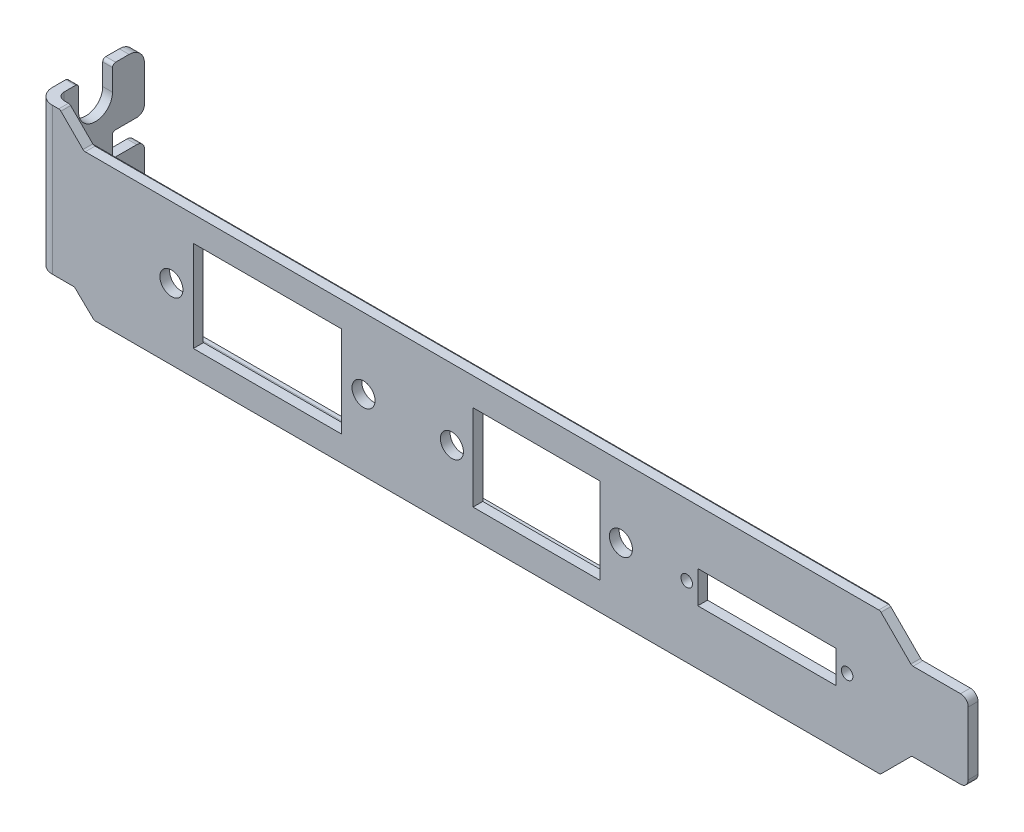
SolidWorks part; units mm, degrees
ref_plane "Front Plane" through (0, 0, 0) normal (0, 0, 1) x (1, 0, 0)
ref_plane "Top Plane" through (0, 0, 0) normal (0, 1, 0) x (1, 0, 0)
ref_plane "Right Plane" through (0, 0, 0) normal (1, 0, 0) x (0, 0, -1)
sketch "Sketch1" plane through (0, 0, 0) normal (0, 0, 1) x (1, 0, 0)
  line L0 (0, 2.48) -> (4.88, 2.48)
  line L5 (7.45, 0) -> (109.76, 0)
  line L6 (0, 2.48) -> (0, 21.53)
  line L7 (6.11, 18.42) -> (109.73, 18.42)
  line L8 (113.85, 4.09) -> (113.85, 14.3) construction
  line L9 (4.88, 2.48) -> (7.45, 0)
  line L10 (109.76, 0) -> (113.85, 4.09)
  line L11 (109.73, 18.42) -> (113.85, 14.3)
  line L12 (6.11, 18.42) -> (3, 21.53)
  line L13 (3, 21.53) -> (0, 21.53)
  line L16 (113.85, 14.3) -> (121.2, 14.3)
  line L18 (113.85, 4.09) -> (121.2, 4.09)
  line L19 (121.2, 14.3) -> (121.2, 4.09)
  dimension "D1" = 7.45
  dimension "D2" = 2.48
  dimension "D3" = 4.88
  dimension "D4" = 106.4
  dimension "D5" = 135
  dimension "D6" = 4.09
  dimension "D7" = 10.21
  dimension "D8" = 135
  dimension "D9" = 18.42
  dimension "D10" = 19.05
  dimension "D11" = 135
  dimension "D12" = 3
  dimension "D13" = 7.35
extrude "Boss-Extrude1" add sketch "Sketch1" along normal blind 1.27
sketch "Sketch8" plane through (0, 0, 0) normal (0, 0, -1) x (-1, 0, 0)
  line L0 (0, 2.48) -> (-4.88, 2.48) construction
  line L1 (0, 21.53) -> (-1.27, 21.53)
  line L2 (0, 21.53) -> (0, 2.48)
  line L3 (0, 2.48) -> (-1.27, 2.48)
  line L4 (-1.27, 21.53) -> (-1.27, 2.48)
  point P7 (0, 0)
  dimension "D1" = 1.27
extrude "Boss-Extrude3" add sketch "Sketch8" along normal blind 11.454
sketch "Sketch9" plane through (0, 0, 0) normal (-1, 0, 0) x (0, 0, 1)
  line L0 (1.27, 21.53) -> (1.27, 2.48) construction
  line L1 (-7.29, 18.35) -> (-7.29, 21.53)
  line L2 (1.27, 21.53) -> (-11.454, 21.53) construction
  line L3 (-7.29, 21.53) -> (-2.87, 21.53)
  line L4 (-2.87, 21.53) -> (-2.87, 18.35)
  line L5 (-11.454, 2.48) -> (-11.454, 21.53) construction
  line L6 (-11.454, 13.91) -> (-7.264, 13.91)
  line L7 (-11.454, 13.91) -> (-11.454, 10.86)
  line L8 (-11.454, 10.86) -> (-7.264, 10.86)
  line L9 (-7.264, 13.91) -> (-7.264, 10.86)
  arc A0 (-7.29, 18.35) -> (-2.87, 18.35) centre (-5.08, 18.35) ccw
  dimension "D3" = 2.21
  dimension "D1" = 6.35
  dimension "D2" = 3.18
  dimension "D4" = 4.19
  dimension "D5" = 3.05
  dimension "D6" = 7.62
extrude "Cut-Extrude6" cut sketch "Sketch9" against normal up to next
ref_plane "Plane1" through (0, 9.21, 0) normal (0, -1, 0) x (-1, 0, 0)
sketch "Sketch10" plane through (0, 0, 0) normal (0, 0, -1) x (-1, 0, 0)
  line L1 (-7, 1.5) -> (-107, 1.5)
  line L2 (-7, 1.5) -> (-7, 3)
  line L3 (-7, 3) -> (-107, 3)
  line L4 (-107, 1.5) -> (-107, 3)
  line L5 (-109, 16) -> (-4, 16)
  line L6 (-109, 16) -> (-109, 17.5)
  line L7 (-109, 17.5) -> (-4, 17.5)
  line L8 (-4, 16) -> (-4, 17.5)
  point P8 (-6.8257, 2.5)
  dimension "D1" = 1.5
  dimension "D2" = 1.5
  dimension "D3" = 7
  dimension "D4" = 100
  dimension "D5" = 4
  dimension "D6" = 16
  dimension "D7" = 105
extrude "Boss-Extrude4" add sketch "Sketch10" along normal blind 1
sketch "Sketch3" plane through (0, 0, 1.27) normal (0, 0, 1) x (1, 0, 0)
  line L1 (17.5, 9.21) -> (42.5, 9.21) construction
  line L2 (20.35, 3.285) -> (39.65, 3.285)
  line L3 (20.35, 3.285) -> (20.35, 15.135)
  line L4 (20.35, 15.135) -> (39.65, 15.135)
  line L5 (39.65, 3.285) -> (39.65, 15.135)
  line L6 (20.35, 3.285) -> (39.65, 15.135) construction
  line L7 (20.35, 15.135) -> (39.65, 3.285) construction
  line L8 (0, 21.53) -> (0, 2.48) construction
  line L9 (-0.6985, 9.21) -> (0.6985, 9.21) construction
  circle A0 centre (17.5, 9.21) radius 1.5
  circle A1 centre (42.5, 9.21) radius 1.5
  point P2 (-22.2505, 0)
  point P3 (22.966, 8.0756)
  point P4 (30, 9.21)
  point P8 (30, 9.21)
  point P15 (0, 0)
  dimension "D2" = 3
  dimension "D3" = 25
  dimension "D1" = 30
  dimension "D4" = 11.85
  dimension "D5" = 19.3
extrude "XT60 cutout" cut sketch "Sketch3" against normal through all
sketch "Sketch5" plane through (0, 0, 1.27) normal (0, 0, 1) x (1, 0, 0)
  line L0 (-0.6985, 9.21) -> (0.6985, 9.21) construction
  line L1 (54, 9.21) -> (76, 9.21) construction
  line L2 (56.75, 3.61) -> (73.25, 3.61)
  line L3 (56.75, 3.61) -> (56.75, 14.81)
  line L4 (56.75, 14.81) -> (73.25, 14.81)
  line L5 (73.25, 3.61) -> (73.25, 14.81)
  line L6 (56.75, 3.61) -> (73.25, 14.81) construction
  line L7 (56.75, 14.81) -> (73.25, 3.61) construction
  circle A0 centre (54, 9.21) radius 1.5
  circle A1 centre (76, 9.21) radius 1.5
  point P2 (-20.1873, 0)
  point P3 (55.2591, 11.8065)
  point P4 (65, 9.21)
  point P8 (65, 9.21)
  dimension "D2" = 3
  dimension "D3" = 22
  dimension "D1" = 65
  dimension "D4" = 11.2
  dimension "D5" = 16.5
extrude "Cut-Extrude4" cut sketch "Sketch5" against normal through all and the other way through all
sketch "Sketch6" plane through (0, 0, 1.27) normal (0, 0, 1) x (1, 0, 0)
  line L0 (84.56, 9.21) -> (105.44, 9.21) construction
  line L1 (86, 7.11) -> (104, 7.11)
  line L2 (86, 7.11) -> (86, 11.31)
  line L3 (86, 11.31) -> (104, 11.31)
  line L4 (104, 7.11) -> (104, 11.31)
  line L5 (86, 7.11) -> (104, 11.31) construction
  line L6 (86, 11.31) -> (104, 7.11) construction
  line L7 (-0.6985, 9.21) -> (0.6985, 9.21) construction
  circle A0 centre (105.44, 9.21) radius 0.75
  circle A1 centre (84.56, 9.21) radius 0.75
  point P0 (95, 9.21)
  point P11 (0, 0)
  point P12 (95, 9.21)
  point P15 (86.7354, 9.21)
  dimension "D4" = 1.5
  dimension "D1" = 18
  dimension "D2" = 4.2
  dimension "D3" = 95
  dimension "D5" = 20.88
extrude "Cut-Extrude5" cut sketch "Sketch6" against normal through all
fillet "Fillet1" radius 0.4 12 edges at (109.76, 0, 0.635) (113.85, 4.09, 0.635) (113.85, 14.3, 0.635) (109.73, 18.42, 0.635) (4.88, 2.48, 0.635) (7.45, 0, 0.635) (3, 21.53, 0.635) (6.11, 18.42, 0.635) (0.635, 21.53, -7.29) (0.635, 21.53, -2.87) (0.635, 10.86, -7.264) (0.635, 13.91, -7.264)
fillet "Fillet2" radius 1 5 edges at (0.635, 13.91, -11.454) (0.635, 10.86, -11.454) (121.2, 14.3, 0.635) (121.2, 4.09, 0.635) (1.27, 12.005, 0)
fillet "Fillet3" radius 2 3 edges at (0, 12.005, 1.27) (0.635, 2.48, -11.454) (0.635, 21.53, -11.454)
fillet "Fillet4" radius 0.5 20 edges at (56.5, 16, 0) (56.5, 17.5, 0) (57, 1.5, 0) (57, 3, 0) (109, 17.5, -0.5) (109, 16.75, -1) (109, 16, -0.5) (109, 16.75, 0) (107, 3, -0.5) (107, 2.25, -1) (107, 1.5, -0.5) (107, 2.25, 0) (4, 16, -0.5) (4, 16.75, -1) (4, 17.5, -0.5) (4, 16.75, 0) (7, 1.5, -0.5) (7, 2.25, -1) (7, 3, -0.5) (7, 2.25, 0)
